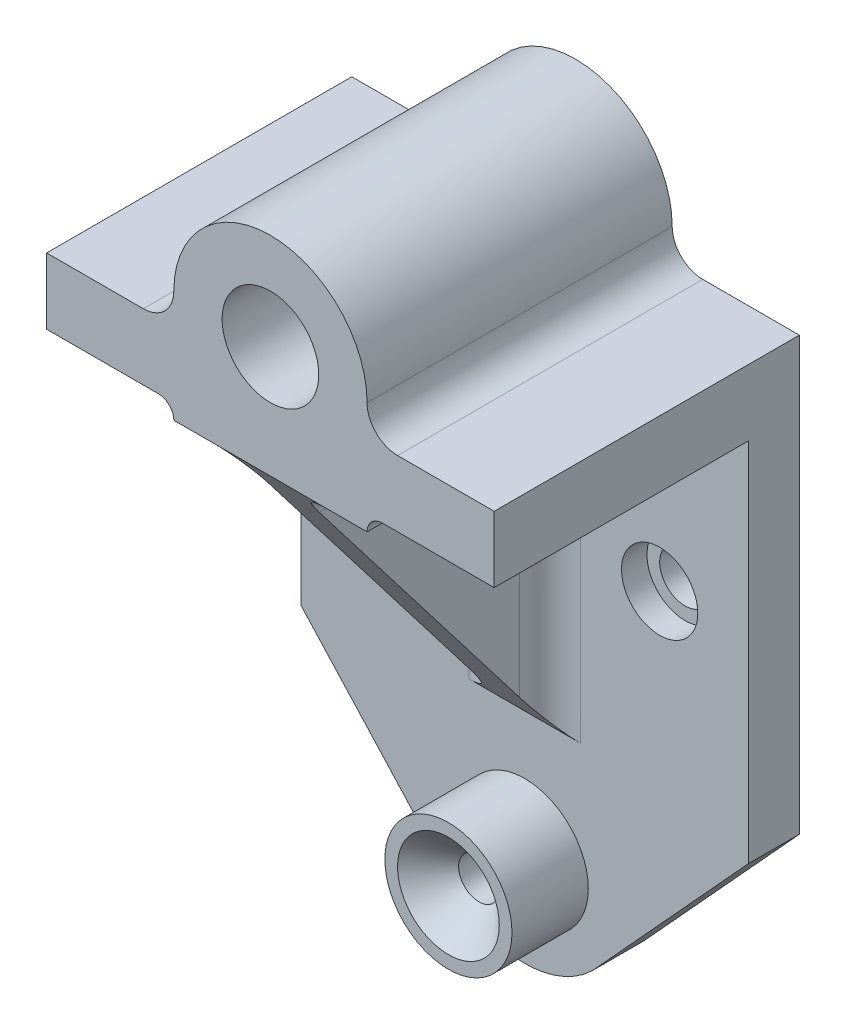
SolidWorks part; units mm, degrees
ref_plane "Front Plane" through (0, 0, 0) normal (0, 0, 1) x (1, 0, 0)
ref_plane "Top Plane" through (0, 0, 0) normal (0, 1, 0) x (1, 0, 0)
ref_plane "Right Plane" through (0, 0, 0) normal (1, 0, 0) x (0, 0, -1)
sketch "Sketch1" plane through (0, 0, 0) normal (0, 0, 1) x (1, 0, 0)
  line L0 (0, 0) -> (38, 0)
  line L1 (38, 0) -> (38, 3)
  line L2 (38, 3) -> (63, 3)
  line L3 (63, 3) -> (63, 16)
  line L4 (63, 16) -> (38, 16)
  line L5 (-25, 16) -> (-25, 3)
  line L6 (-25, 3) -> (0, 3)
  line L7 (0, 3) -> (0, 0)
  line L8 (0, 16) -> (-25, 16)
  line L9 (0, 22) -> (0, 16)
  line L10 (38, 22) -> (38, 16)
  circle A0 centre (19, 22) radius 9.5
  arc A1 (38, 22) -> (0, 22) centre (19, 22) ccw
  dimension "D2" = 19
  dimension "D3" = 22
  dimension "19" = 19
  dimension "D1" = 13
  dimension "D4" = 3
  dimension "D5" = 88
  dimension "D6" = 44
  dimension "D7" = 25
  dimension "D8" = 25
extrude "Boss-Extrude1" add sketch "Sketch1" along normal blind 60
sketch "Sketch2" plane through (0, 0, 0) normal (0, 0, 1) x (1, 0, 0)
  line L0 (63, 3) -> (63, -69)
  line L1 (63, -69) -> (32.3856, -102.4843)
  line L2 (-25, 3) -> (-25, -69)
  line L3 (-25, -69) -> (4.5204, -101.3021)
  line L4 (19, 23.7819) -> (19, -107.909) construction
  line L5 (0, 16) -> (-25, 16) construction
  line L6 (-25, 3) -> (0, 3) construction
  line L7 (-25, 3) -> (0, 3)
  line L8 (0, 3) -> (0, 0)
  line L9 (0, 0) -> (38, 0)
  line L10 (38, 0) -> (38, 3)
  line L11 (38, 3) -> (63, 3)
  circle A0 centre (19, -89) radius 12.5
  arc A1 (4.5204, -101.3021) -> (33.6265, -101.127) centre (19, -89) ccw
  dimension "D1" = 25
  dimension "D2" = 38
  dimension "D4" = 105
  dimension "D5" = 72
extrude "Boss-Extrude2" add sketch "Sketch2" along normal blind 10 contours L9 L4 A0 A1 L1 L0 L11 L10 | L4 L9 L8 L7 L2 L3 A1 A0
fillet "Fillet1" radius 6 1 edges at (0, 16, 30)
fillet "Fillet2" radius 6 1 edges at (38, 16, 30)
fillet "Fillet3" radius 3 2 edges at (0, 3, 35) (38, 3, 35)
ref_plane "Plane1" through (19, 0, 0) normal (1, 0, 0) x (0, 0, -1)
sketch "Sketch4" plane through (19, 0, 0) normal (1, 0, 0) x (0, 0, -1)
  line L0 (-60, 0) -> (-10, -65)
  line L1 (-10, 3) -> (-10, -69) construction
  line L2 (-10, -65) -> (-10, 0)
  line L3 (-10, 0) -> (-60, 0)
  dimension "D1" = 65
extrude "Boss-Extrude4" add sketch "Sketch4" along normal mid plane 10
fillet "Fillet4" radius 6 2 edges at (14, 0, 35) (24, 0, 35)
fillet "Fillet5" radius 6 2 edges at (24, -35.5, 10) (14, -35.5, 10)
ref_plane "Plane2" through (0, 0, 5) normal (0, 0, 1) x (1, 0, 0)
sketch "Sketch6" plane through (0, 0, 5) normal (0, 0, 1) x (1, 0, 0)
  circle A0 centre (19, -89) radius 12.5
extrude "Boss-Extrude5" add sketch "Sketch6" along normal mid plane 40
hole_wizard "Hole2" positions "Sketch10" profile "Sketch12" legacy end condition through all
sketch "Sketch10" plane through (0, 0, 25) normal (0, 0, 1) x (1, 0, 0)
  point P0 (19, -89)
sketch "Sketch12" plane through (19, -89, 25) normal (1, 0, 0) x (0, -1, 0)
  line L0 (0, 0) -> (0, 39.5474)
  line L1 (0, 39.5474) -> (4, 39.5474)
  line L2 (4, 39.5474) -> (4, 6)
  line L3 (4, 6) -> (10, 0)
  line L4 (10, 0) -> (0, 0)
  line L5 (0, -6.4453) -> (0, 115.525) construction
  line L6 (-4, 6) -> (-10, 0) construction
  dimension "Diameter" = 8
  dimension "Depth" = 40
  dimension "C-Sink Angle" = 90
  dimension "C-Sink Diameter" = 20
sketch "Sketch13" plane through (0, 0, -14.5474) normal (0, 0, 1) x (1, 0, 0)
  circle A0 centre (19, -89) radius 4
extrude "Cut-Extrude1" cut sketch "Sketch13" against normal blind 40
hole_wizard "Hole4" positions "3DSketch8" profile "Sketch25" legacy end condition up to next
sketch3d "3DSketch8"
  point P0 (-7.5364, -31.3519, 10)
sketch "Sketch25" plane through (-7.5364, -31.3519, 10) normal (1, 0, 0) x (0, -1, 0)
  line L0 (0, 0) -> (0, 10.001)
  line L1 (0, 10.001) -> (5, 10.001)
  line L2 (5, 10.001) -> (5, 5)
  line L3 (5, 5) -> (7.5, 5)
  line L4 (7.5, 5) -> (7.5, 0)
  line L5 (7.5, 0) -> (0, 0)
  line L6 (0, 110) -> (0, -10) construction
  dimension "Diameter" = 10
  dimension "Depth" = 10.001
  dimension "C-Bore Diameter" = 15
  dimension "C-Bore Depth" = 5
mirror "Mirror2" about plane through (19, 0, 0) normal (1, 0, 0) of "Hole4"
